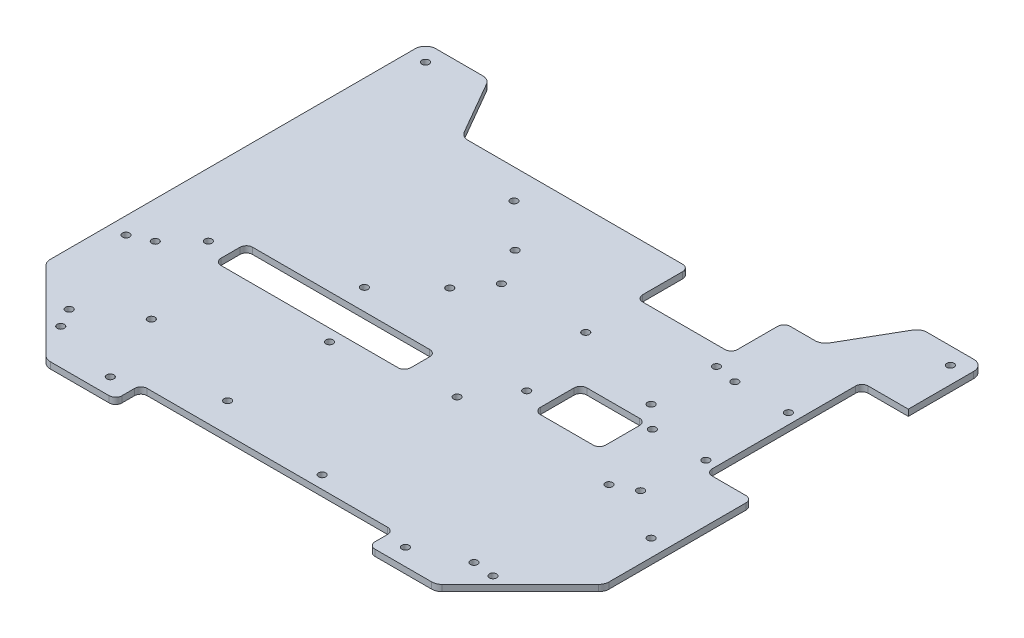
SolidWorks part; units mm, degrees
material "Acier non allié"
ref_plane "Front" through (0, 0, 0) normal (0, 0, 1) x (1, 0, 0)
ref_plane "Top" through (0, 0, 0) normal (0, 1, 0) x (1, 0, 0)
ref_plane "Right" through (0, 0, 0) normal (1, 0, 0) x (0, 0, -1)
sketch "Esquisse1" plane through (0, 0, 0) normal (0, 1, 0) x (1, 0, 0)
  line L0 (0, 0) -> (0, 190) construction
  line L1 (-92.5, 0) -> (92.5, 0)
  line L2 (92.5, 0) -> (132.5, 40)
  line L3 (132.5, 40) -> (132.5, 220)
  line L4 (132.5, 220) -> (102.5, 220)
  line L5 (102.5, 220) -> (85.1795, 190)
  line L6 (85.1795, 190) -> (-85.1795, 190)
  line L7 (-102.5, 220) -> (-85.1795, 190)
  line L8 (-132.5, 220) -> (-102.5, 220)
  line L9 (-132.5, 40) -> (-132.5, 220)
  line L10 (-92.5, 0) -> (-132.5, 40)
  dimension "D1" = 132.5
  dimension "D2" = 220
  dimension "D3" = 60
  dimension "D4" = 30
  dimension "D5" = 40
  dimension "D6" = 40
  dimension "D7" = 30
extrude "Boss.-Extru.1" add sketch "Esquisse1" along normal blind 3
fillet "Congé1" radius 5 10 edges at (92.5, 1.5, 0) (132.5, 1.5, -40) (132.5, 1.5, -220) (102.5, 1.5, -220) (85.1795, 1.5, -190) (-85.1795, 1.5, -190) (-102.5, 1.5, -220) (-132.5, 1.5, -220) (-92.5, 1.5, 0) (-132.5, 1.5, -40)
sketch "Esquisse2" plane through (0, 3, 0) normal (0, 1, 0) x (1, 0, 0)
  line L0 (0, 0) -> (0, 294.1173) construction
  line L2 (-90.4289, 0) -> (90.4289, 0) construction
  circle A0 centre (70, 8) radius 1
  circle A1 centre (124.5, 70) radius 1
  circle A2 centre (124.5, 212) radius 1
  circle A3 centre (-124.5, 212) radius 1
  circle A4 centre (-124.5, 70) radius 1
  circle A5 centre (-70, 8) radius 1
  dimension "D2" = 2
  dimension "D6" = 2
  dimension "D9" = 2
  dimension "D1" = 70
  dimension "D3" = 8
  dimension "D4" = 124.5
  dimension "D5" = 70
  dimension "D7" = 124.5
  dimension "D8" = 212
extrude "Enlèv. mat.-Extru.1" cut sketch "Esquisse2" against normal blind 3
hole_wizard "Dégagement M31" positions "Esquisse3" profile "Esquisse4" hole size "M3" standard "ISO" end condition through all
sketch "Esquisse3" plane through (0, 3, 0) normal (0, 1, 0) x (1, 0, 0)
  point P0 (70, 8)
  point P3 (-70, 8)
  point P6 (-124.5, 70)
  point P9 (-124.5, 212)
  point P12 (124.5, 212)
  point P15 (124.5, 70)
sketch "Esquisse4" plane through (70, 3, -8) normal (1, 0, 0) x (0, 0, 1)
  line L0 (0, 0) -> (0, 3)
  line L1 (0, 3) -> (1.7, 3)
  line L2 (1.7, 3) -> (1.7, 0)
  line L5 (1.7, 0) -> (0, 0)
  line L11 (0, -6.35) -> (0, 107.95) construction
  dimension "Diamètre du perçage jusqu'au prochain" = 3.4
  dimension "Profondeur du perçage jusqu'au prochain" = 3
sketch "Esquisse5" plane through (0, 3, 0) normal (0, 1, 0) x (1, 0, 0)
  line L0 (82.2927, 190) -> (-82.2927, 190) construction
  line L1 (67.5, 190) -> (22.5, 190)
  line L2 (67.5, 190) -> (67.5, 165)
  line L3 (67.5, 165) -> (22.5, 165)
  line L4 (22.5, 190) -> (22.5, 165)
  line L5 (132.5, 42.0711) -> (132.5, 215) construction
  line L6 (132.5, 184) -> (110.5, 184)
  line L7 (132.5, 184) -> (132.5, 110)
  line L8 (132.5, 110) -> (110.5, 110)
  line L9 (110.5, 184) -> (110.5, 110)
  line L10 (127.5, 220) -> (105.3868, 220) construction
  dimension "D1" = 25
  dimension "D2" = 65
  dimension "D3" = 110
  dimension "D4" = 36
  dimension "D5" = 110
  dimension "D6" = 22
extrude "Enlèv. mat.-Extru.2" cut sketch "Esquisse5" against normal through all
fillet "Congé2" radius 3 7 edges at (132.5, 1.5, -110) (110.5, 1.5, -110) (110.5, 1.5, -184) (67.5, 1.5, -190) (67.5, 1.5, -165) (22.5, 1.5, -165) (22.5, 1.5, -190)
sketch "Esquisse6" plane through (0, 3, 0) normal (0, 1, 0) x (1, 0, 0)
  line L0 (110.5, 140.5) -> (-167.6757, 140.5) construction
  line L1 (110.5, 181) -> (110.5, 113) construction
  line L2 (-90.4289, 0) -> (90.4289, 0) construction
  line L3 (110.5, 181) -> (110.5, 113) construction
  circle A0 centre (69.5, 156) radius 1
  circle A1 centre (-26, 156) radius 1
  circle A2 centre (-46.5, 176) radius 1
  circle A3 centre (69.5, 125) radius 1
  circle A4 centre (-26, 125) radius 1
  circle A5 centre (-46.5, 105) radius 1
  dimension "D4" = 2
  dimension "D6" = 2
  dimension "D10" = 2
  dimension "D1" = 140.5
  dimension "D2" = 41
  dimension "D3" = 15.5
  dimension "D5" = 136.5
  dimension "D7" = 15.5
  dimension "D8" = 35.5
  dimension "D9" = 157
extrude "Enlèv. mat.-Extru.3" cut sketch "Esquisse6" against normal through all
hole_wizard "Dégagement M32" positions "Esquisse7" profile "Esquisse8" hole size "M3" standard "ISO"
sketch "Esquisse7" plane through (0, 3, 0) normal (0, 1, 0) x (1, 0, 0)
  point P0 (-46.5, 105)
  point P3 (-26, 125)
  point P6 (-26, 156)
  point P9 (-46.5, 176)
  point P12 (69.5, 156)
  point P15 (69.5, 125)
sketch "Esquisse8" plane through (-46.5, 3, -105) normal (1, 0, 0) x (0, 0, 1)
  line L0 (0, 0) -> (0, 11.0215)
  line L1 (0, 11.0215) -> (1.7, 10)
  line L2 (1.7, 10) -> (1.7, 0)
  line L5 (1.7, 0) -> (0, 0)
  line L10 (0, 11.0215) -> (-1.7, 10) construction
  line L11 (0, -6.35) -> (0, 107.95) construction
  dimension "Diamètre du perçage" = 3.4
  dimension "Profondeur du perçage" = 10
  dimension "Angle de pointe" = 118
sketch "Esquisse9" plane through (0, 3, 0) normal (0, 1, 0) x (1, 0, 0)
  line L0 (132.5, 42.0711) -> (132.5, 107) construction
  line L1 (-90.4289, 0) -> (90.4289, 0) construction
  line L2 (-107.5, 26) -> (-32.37, 26) construction
  line L7 (20.5, 18) -> (20.5, 82) construction
  line L8 (25.5, 165) -> (64.5, 165) construction
  line L9 (24.5, 139) -> (-15.5, 139) construction
  line L10 (110.5, 181) -> (110.5, 113) construction
  line L11 (113.5, 110) -> (129.5, 110) construction
  line L13 (-32.37, 26) -> (-32.37, 74.3362) construction
  line L14 (-32.37, 74.3362) -> (-115, 74.3362) construction
  line L15 (-132.5, 215) -> (-132.5, 42.0711) construction
  circle A0 centre (105.5, 115) radius 1
  circle A3 centre (105.5, 154.12) radius 1
  circle A10 centre (20.5, 82) radius 1
  circle A11 centre (92.5, 82) radius 1
  circle A12 centre (20.5, 18) radius 1
  circle A13 centre (92.5, 18) radius 1
  circle A14 centre (-15.5, 139) radius 1
  circle A15 centre (24.5, 139) radius 1
  circle A16 centre (34.5, 101) radius 1
  circle A17 centre (80.1, 115) radius 1
  circle A18 centre (80.1, 154.12) radius 1
  circle A19 centre (-107.5, 26) radius 1.5
  circle A21 centre (-32.37, 26) radius 1.5
  circle A22 centre (-32.37, 74.3362) radius 1.5
  circle A23 centre (-115, 74.3362) radius 1.5
  circle A24 centre (-83.99, 41.44) radius 1.5
  dimension "D2" = 2
  dimension "D4" = 2
  dimension "D21" = 2
  dimension "D22" = 2
  dimension "D23" = 2
  dimension "D24" = 2
  dimension "D32" = 2
  dimension "D33" = 2
  dimension "D34" = 2
  dimension "D11" = 2
  dimension "D12" = 2
  dimension "D17" = 3
  dimension "D18" = 3
  dimension "D19" = 3
  dimension "D36" = 3
  dimension "D42" = 3
  dimension "D5" = 27
  dimension "25" = 27
  dimension "D10" = 39.12
  dimension "D25" = 72
  dimension "D26" = 72
  dimension "D27" = 64
  dimension "D28" = 64
  dimension "D30" = 18
  dimension "D31" = 18
  dimension "D37" = 40
  dimension "D39" = 10
  dimension "D7" = 5
  dimension "D8" = 25.4
  dimension "D9" = 25.4
  dimension "D40" = 39.12
  dimension "D38" = 76
  dimension "D6" = 38
  dimension "D35" = 26
  dimension "D14" = 40
  dimension "D13" = 75.13
  dimension "D15" = 82.63
  dimension "D16" = 48.3362
  dimension "D20" = 26
  dimension "D29" = 25
  dimension "D41" = 23.51
  dimension "D43" = 15.44
extrude "Enlèv. mat.-Extru.4" cut sketch "Esquisse9" against normal through all
hole_wizard "Dégagement M33" positions "Esquisse10" profile "Esquisse11" hole size "M3" standard "ISO"
sketch "Esquisse10" plane through (0, 3, 0) normal (0, 1, 0) x (1, 0, 0)
  point P3 (105.5, 115)
  point P9 (105.5, 154.12)
  point P14 (80.1, 154.12)
  point P17 (80.1, 115)
sketch "Esquisse11" plane through (105.5, 3, -115) normal (1, 0, 0) x (0, 0, 1)
  line L0 (0, 0) -> (0, 11.0215)
  line L1 (0, 11.0215) -> (1.7, 10)
  line L2 (1.7, 10) -> (1.7, 0)
  line L5 (1.7, 0) -> (0, 0)
  line L10 (0, 11.0215) -> (-1.7, 10) construction
  line L11 (0, -6.35) -> (0, 107.95) construction
  dimension "Diamètre du perçage" = 3.4
  dimension "Profondeur du perçage" = 10
  dimension "Angle de pointe" = 118
sketch "Esquisse12" plane through (0, 3, 0) normal (0, 1, 0) x (1, 0, 0)
  line L2 (-90.4289, 0) -> (90.4289, 0) construction
  line L3 (102.5, 17) -> (-102.5, 17) construction
  line L4 (102.5, 17) -> (102.5, 87) construction
  line L5 (102.5, 87) -> (-102.5, 87) construction
  line L6 (-102.5, 17) -> (-102.5, 87) construction
  line L7 (132.5, 42.0711) -> (132.5, 107) construction
  circle A4 centre (-102.5, 87) radius 1
  circle A5 centre (102.5, 87) radius 1
  circle A6 centre (102.5, 17) radius 1
  circle A7 centre (-102.5, 17) radius 1
  point P6 (102.5, 52)
  dimension "D5" = 2
  dimension "D6" = 2
  dimension "D7" = 2
  dimension "D8" = 2
  dimension "D1" = 70
  dimension "D2" = 205
  dimension "D3" = 17
  dimension "D4" = 30
extrude "Enlèv. mat.-Extru.5" cut sketch "Esquisse12" against normal through all and the other way through all
hole_wizard "Dégagement M34" positions "Esquisse13" profile "Esquisse14" hole size "M3" standard "ISO"
sketch "Esquisse13" plane through (0, 3, 0) normal (0, 1, 0) x (1, 0, 0)
  point P16 (20.5, 18)
  point P19 (92.5, 18)
  point P22 (20.5, 82)
  point P25 (92.5, 82)
  point P29 (34.5, 101)
  point P32 (24.5, 139)
  point P35 (-15.5, 139)
  point P38 (-115, 74.3362)
  point P41 (-32.37, 74.3362)
  point P44 (-107.5, 26)
  point P47 (-32.37, 26)
  point P50 (-83.99, 41.44)
sketch "Esquisse14" plane through (20.5, 3, -18) normal (1, 0, 0) x (0, 0, 1)
  line L0 (0, 0) -> (0, 11.0215)
  line L1 (0, 11.0215) -> (1.7, 10)
  line L2 (1.7, 10) -> (1.7, 0)
  line L5 (1.7, 0) -> (0, 0)
  line L10 (0, 11.0215) -> (-1.7, 10) construction
  line L11 (0, -6.35) -> (0, 107.95) construction
  dimension "Diamètre du perçage" = 3.4
  dimension "Profondeur du perçage" = 10
  dimension "Angle de pointe" = 118
hole_wizard "Dégagement M35" positions "Esquisse15" profile "Esquisse16" hole size "M3" standard "ISO"
sketch "Esquisse15" plane through (0, 3, 0) normal (0, 1, 0) x (1, 0, 0)
  point P0 (-102.5, 17)
  point P3 (-102.5, 87)
  point P6 (102.5, 87)
  point P9 (102.5, 17)
sketch "Esquisse16" plane through (-102.5, 3, -17) normal (1, 0, 0) x (0, 0, 1)
  line L0 (0, 0) -> (0, 11.0215)
  line L1 (0, 11.0215) -> (1.7, 10)
  line L2 (1.7, 10) -> (1.7, 0)
  line L5 (1.7, 0) -> (0, 0)
  line L10 (0, 11.0215) -> (-1.7, 10) construction
  line L11 (0, -6.35) -> (0, 107.95) construction
  dimension "Diamètre du perçage" = 3.4
  dimension "Profondeur du perçage" = 10
  dimension "Angle de pointe" = 118
sketch "Esquisse17" plane through (0, 3, 0) normal (0, 1, 0) x (1, 0, 0)
  line L0 (-90.4289, 0) -> (90.4289, 0) construction
  line L1 (-92.5, 95) -> (-2.5, 95)
  line L2 (-92.5, 95) -> (-92.5, 80)
  line L3 (-92.5, 80) -> (-2.5, 80)
  line L4 (-2.5, 95) -> (-2.5, 80)
  line L5 (-132.5, 215) -> (-132.5, 42.0711) construction
  line L6 (132.5, 42.0711) -> (132.5, 107) construction
  line L7 (44.5, 116.5) -> (75.5, 116.5)
  line L8 (44.5, 116.5) -> (44.5, 94.5)
  line L9 (44.5, 94.5) -> (75.5, 94.5)
  line L10 (75.5, 116.5) -> (75.5, 94.5)
  line L11 (82.2927, 190) -> (70.5, 190) construction
  line L13 (-59.5, 12) -> (60.5, 12)
  line L14 (-59.5, 12) -> (-59.5, 0)
  line L15 (-59.5, 0) -> (60.5, 0)
  line L16 (60.5, 12) -> (60.5, 0)
  dimension "D1" = 90
  dimension "D2" = 15
  dimension "D3" = 80
  dimension "D4" = 40
  dimension "D5" = 31
  dimension "D6" = 22
  dimension "D7" = 57
  dimension "D8" = 73.5
  dimension "D9" = 12
  dimension "D11" = 120
  dimension "D12" = 72
extrude "Enlèv. mat.-Extru.6" cut sketch "Esquisse17" against normal up to surface (3 mm away) up to face at (-102.5, 0, -15.3)
fillet "Congé3" radius 3 12 edges at (60.5, 1.5, 0) (60.5, 1.5, -12) (-59.5, 1.5, -12) (-59.5, 1.5, 0) (44.5, 1.5, -116.5) (75.5, 1.5, -116.5) (75.5, 1.5, -94.5) (44.5, 1.5, -94.5) (-92.5, 1.5, -80) (-2.5, 1.5, -80) (-2.5, 1.5, -95) (-92.5, 1.5, -95)
equation "\"WIDTH\"= 300mm'Total width of the robot"
equation "\"LENGTH\"= 220mm'Total length of the robot"
equation "\"CUT_DEPTH\"= 45mm'Depth of the cut on the edges of the plate"
equation "\"Plate_th\"= 3mm'Thickness of the plate"
equation "\"D1\"= \"Plate_th\""
equation "\"D5@Esquisse9\"=\"25@Esquisse9\""
